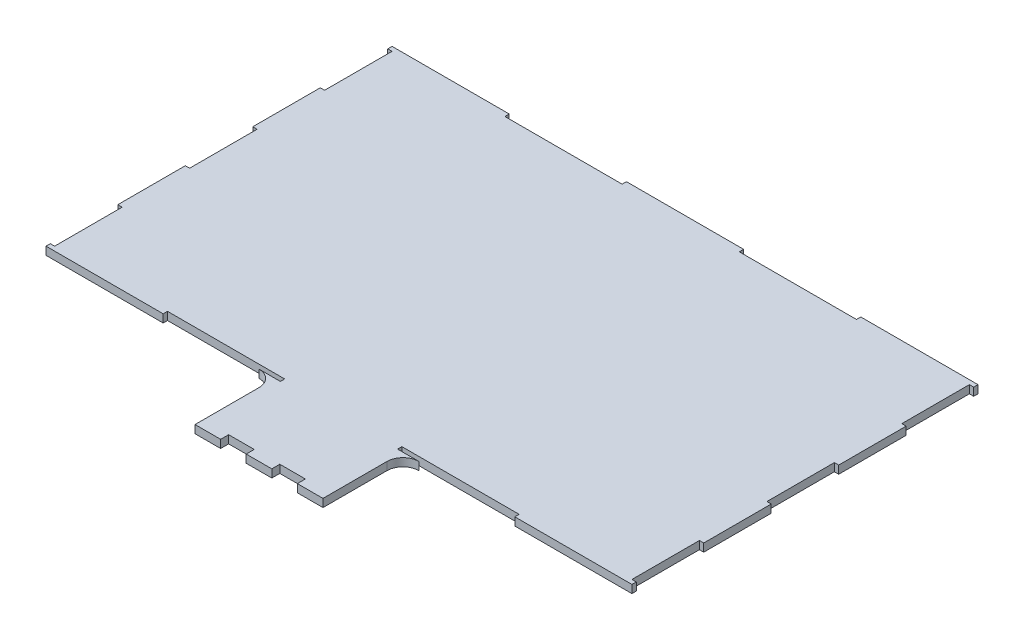
SolidWorks part; units mm, degrees
ref_plane "Front Plane" through (0, 0, 0) normal (0, 0, 1) x (1, 0, 0)
ref_plane "Top Plane" through (0, 0, 0) normal (0, 1, 0) x (1, 0, 0)
ref_plane "Right Plane" through (0, 0, 0) normal (1, 0, 0) x (0, 0, -1)
sketch "Sketch1" plane through (0, 0, 0) normal (0, 1, 0) x (1, 0, 0)
  line L0 (-183.2, 108.2) -> (-109.92, 108.2)
  line L1 (-109.92, 105.5) -> (-36.64, 105.5)
  line L4 (180.5, 105.5) -> (180.5, 63.3)
  line L5 (183.2, 108.2) -> (183.2, 105.5)
  line L8 (183.2, 63.3) -> (183.2, 21.1)
  line L9 (183.2, 108.2) -> (183.2, -108.2) construction
  line L10 (180.5, -105.5) -> (183.2, -105.5)
  line L11 (180.5, 105.5) -> (183.2, 105.5)
  line L13 (180.5, 105.5) -> (180.5, -105.5) construction
  line L14 (180.5, 21.1) -> (180.5, -21.1)
  line L16 (180.5, -63.3) -> (180.5, -105.5)
  line L18 (-180.5, 105.5) -> (-180.5, -105.5) construction
  line L23 (-183.2, 108.2) -> (183.2, 108.2) construction
  line L24 (-36.64, 108.2) -> (36.64, 108.2)
  line L26 (109.92, 108.2) -> (183.2, 108.2)
  line L27 (-109.92, 108.2) -> (-109.92, 105.5)
  line L28 (-36.64, 108.2) -> (-36.64, 105.5)
  line L29 (36.64, 108.2) -> (36.64, 105.5)
  line L30 (109.92, 108.2) -> (109.92, 105.5)
  line L31 (-180.5, 105.5) -> (180.5, 105.5) construction
  line L32 (36.64, 105.5) -> (109.92, 105.5)
  line L33 (-183.2, -108.2) -> (183.2, -108.2) construction
  line L34 (-180.5, -105.5) -> (180.5, -105.5) construction
  line L35 (180.5, -21.1) -> (183.2, -21.1)
  line L36 (109.92, -108.2) -> (183.2, -108.2)
  line L37 (109.92, -108.2) -> (109.92, -105.5)
  line L38 (36.64, -105.5) -> (109.92, -105.5)
  line L39 (36.64, -108.2) -> (36.64, -105.5)
  line L41 (-36.64, -108.2) -> (-36.64, -105.5)
  line L42 (-109.92, -105.5) -> (-36.64, -105.5)
  line L43 (-109.92, -108.2) -> (-109.92, -105.5)
  line L44 (-183.2, -108.2) -> (-109.92, -108.2)
  line L45 (180.5, -63.3) -> (183.2, -63.3)
  line L46 (180.5, 21.1) -> (183.2, 21.1)
  line L47 (180.5, 63.3) -> (183.2, 63.3)
  line L48 (183.2, -21.1) -> (183.2, -63.3)
  line L49 (-183.2, 108.2) -> (-183.2, -108.2) construction
  line L50 (183.2, -105.5) -> (183.2, -108.2)
  line L51 (-40, -118.2) -> (-40, -158.2)
  line L52 (-183.2, -105.5) -> (-183.2, -108.2)
  line L53 (-180.5, -105.5) -> (-183.2, -105.5)
  line L54 (-180.5, -63.3) -> (-180.5, -105.5)
  line L55 (-180.5, -63.3) -> (-183.2, -63.3)
  line L56 (-183.2, -21.1) -> (-183.2, -63.3)
  line L57 (-180.5, -21.1) -> (-183.2, -21.1)
  line L58 (-180.5, 21.1) -> (-180.5, -21.1)
  line L59 (-180.5, 21.1) -> (-183.2, 21.1)
  line L60 (-183.2, 63.3) -> (-183.2, 21.1)
  line L61 (-180.5, 63.3) -> (-183.2, 63.3)
  line L62 (-180.5, 105.5) -> (-180.5, 63.3)
  line L63 (-183.2, 108.2) -> (-183.2, 105.5)
  line L64 (-180.5, 105.5) -> (-183.2, 105.5)
  line L65 (-36.64, -108.2) -> (-40, -108.2)
  line L66 (36.64, -108.2) -> (40, -108.2)
  line L67 (40, -118.2) -> (40, -158.2)
  line L70 (-40, -158.2) -> (-24, -158.2)
  line L71 (24, -153.2) -> (8, -153.2)
  line L73 (50, -108.2) -> (40, -108.2)
  line L74 (-40, -108.2) -> (-50, -108.2)
  line L75 (-8, -158.2) -> (8, -158.2)
  line L77 (24, -158.2) -> (40, -158.2)
  line L78 (-24, -158.2) -> (-24, -153.2)
  line L79 (-8, -158.2) -> (-8, -153.2)
  line L80 (8, -158.2) -> (8, -153.2)
  line L81 (24, -158.2) -> (24, -153.2)
  line L82 (-8, -153.2) -> (-24, -153.2)
  arc A0 (-50, -108.2) -> (-40, -118.2) centre (-50, -118.2) cw
  arc A1 (40, -118.2) -> (50, -108.2) centre (50, -118.2) cw
  point P0 (0, 0)
  dimension "D2" = 10
  dimension "D3" = 10
  dimension "D1" = 2.7
  dimension "D4" = 40
  dimension "D5" = 40
extrude "Boss-Extrude1" add sketch "Sketch1" along normal blind 5
